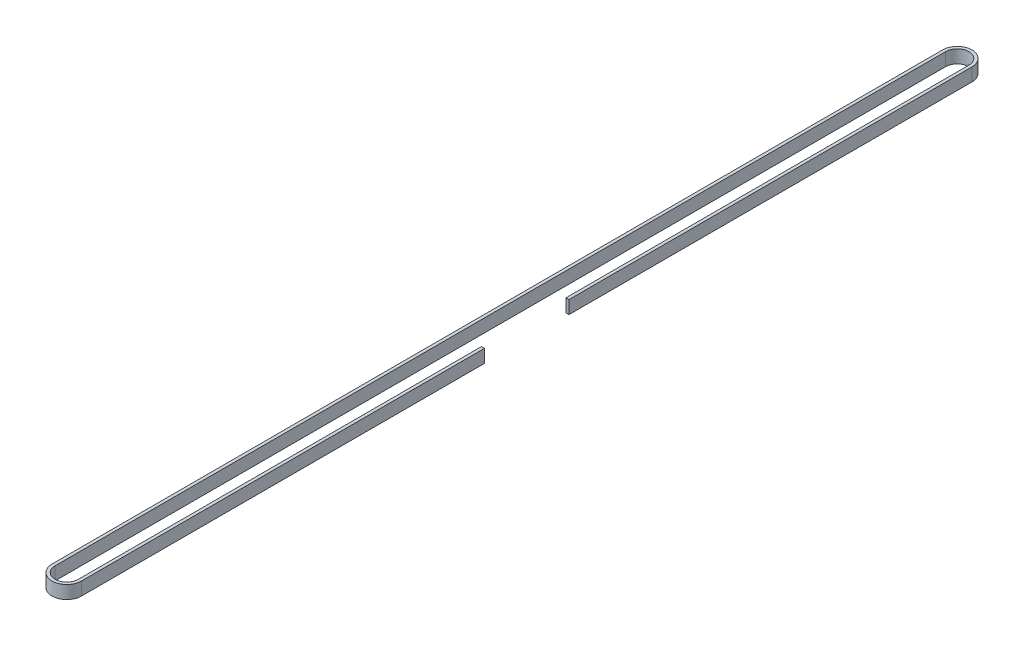
SolidWorks part; units mm, degrees
ref_plane "Front Plane" through (0, 0, 0) normal (0, 0, 1) x (1, 0, 0)
ref_plane "Top Plane" through (0, 0, 0) normal (0, 1, 0) x (1, 0, 0)
ref_plane "Right Plane" through (0, 0, 0) normal (1, 0, 0) x (0, 0, -1)
sketch "Sketch1" plane through (0, 0, 0) normal (0, 1, 0) x (1, 0, 0)
  line L0 (344.01, -294.7675) -> (344.01, 113.9825)
  line L1 (356.75, 113.9825) -> (356.75, -71.0175)
  line L2 (356.75, -294.7675) -> (356.75, -109.7675)
  arc A0 (356.75, -294.7675) -> (344.01, -294.7675) centre (350.38, -294.7675) cw
  arc A1 (356.75, 113.9825) -> (344.01, 113.9825) centre (350.38, 113.9825) ccw
  dimension "D1" = 6.37
  dimension "D2" = 408.75
  dimension "D3" = 185
extrude "Extrude-Thin1" add sketch "Sketch1" along normal blind 6 thin thin type two direction wall 0.376 second wall 1.004
